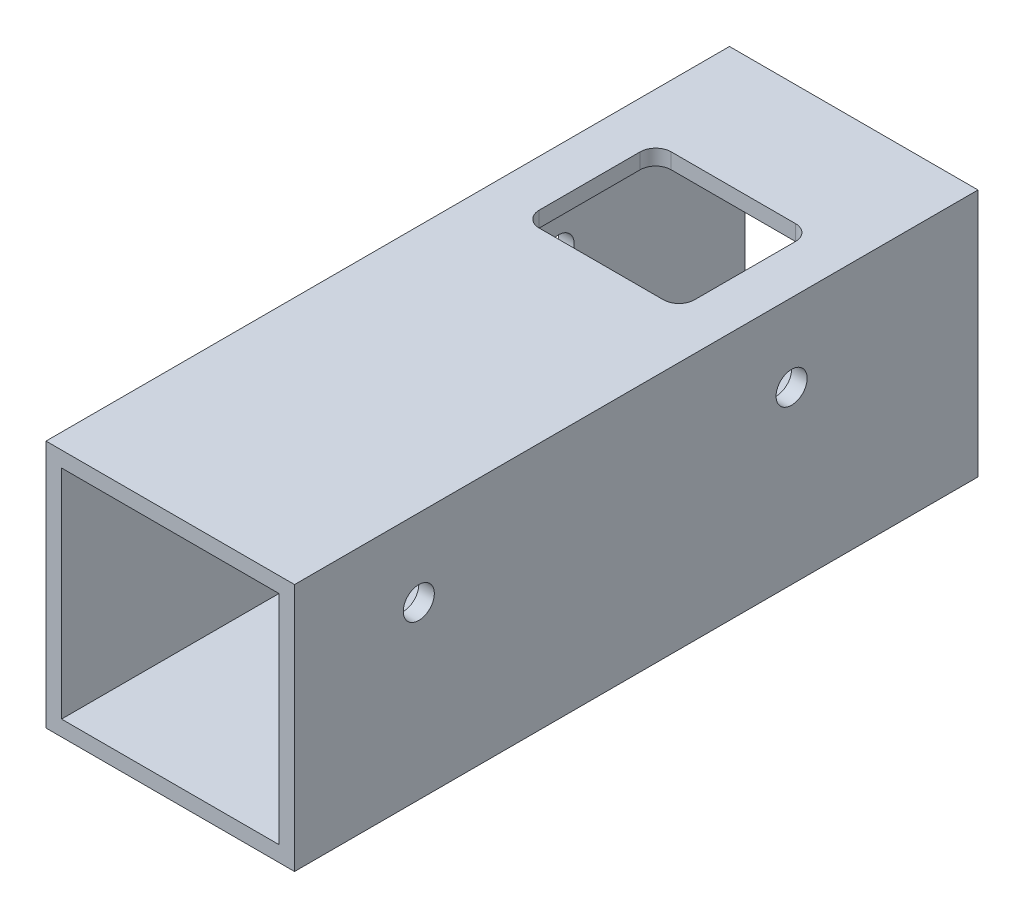
SolidWorks part; units mm, degrees
material "6061-T6 (SS)"
ref_plane "Front Plane" through (0, 0, 0) normal (0, 0, 1) x (1, 0, 0)
ref_plane "Top Plane" through (0, 0, 0) normal (0, 1, 0) x (1, 0, 0)
ref_plane "Right Plane" through (0, 0, 0) normal (1, 0, 0) x (0, 0, -1)
sketch "Sketch1" plane through (0, 0, 0) normal (0, 0, 1) x (1, 0, 0)
  line L1 (-25.4, -25.4) -> (25.4, -25.4)
  line L2 (-25.4, -25.4) -> (-25.4, 25.4)
  line L3 (-25.4, 25.4) -> (25.4, 25.4)
  line L4 (25.4, -25.4) -> (25.4, 25.4)
  line L5 (-25.4, -25.4) -> (25.4, 25.4) construction
  line L6 (-25.4, 25.4) -> (25.4, -25.4) construction
  point P0 (0, 0)
  dimension "D1" = 50.8
  dimension "D2" = 50.8
extrude "Boss-Extrude1" add sketch "Sketch1" along normal mid plane 139.7
shell "Shell1" thickness 3.175 removed face at (0, 0, -69.85) removed face at (0, 0, 69.85)
sketch "Sketch2" plane through (0, 0, 0) normal (0, 1, 0) x (1, 0, 0)
  line L0 (25.4, 69.85) -> (-25.4, 69.85) construction
  line L1 (15.875, 45.2437) -> (-15.875, 45.2437)
  line L2 (15.875, 45.2437) -> (15.875, 18.2563)
  line L3 (15.875, 18.2563) -> (-15.875, 18.2563)
  line L4 (-15.875, 45.2437) -> (-15.875, 18.2563)
  line L5 (25.4, -69.85) -> (-25.4, -69.85) construction
  point P4 (0, 45.2437)
  point P7 (0, 69.85)
  point P9 (15.875, 31.75)
  dimension "D1" = 31.75
  dimension "D2" = 26.9875
  dimension "D3" = 101.6
extrude "Cut-Extrude1" cut sketch "Sketch2" along normal through all
fillet "Fillet1" radius 3.175 4 edges at (15.875, 23.8125, -45.2437) (-15.875, 23.8125, -45.2437) (-15.875, 23.8125, -18.2563) (15.875, 23.8125, -18.2563)
sketch "Sketch3" plane through (0, 0, 0) normal (1, 0, 0) x (0, 0, -1)
  line L1 (-69.85, 25.4) -> (-69.85, -25.4) construction
  line L2 (-69.85, 25.4) -> (69.85, 25.4) construction
  circle A0 centre (31.75, 9.525) radius 3.175
  circle A1 centre (-44.45, 9.525) radius 3.175
  dimension "D1" = 6.35
  dimension "D2" = 25.4
  dimension "D3" = 76.2
  dimension "D4" = 15.875
extrude "Cut-Extrude2" cut sketch "Sketch3" against normal through all both and the other way through all
